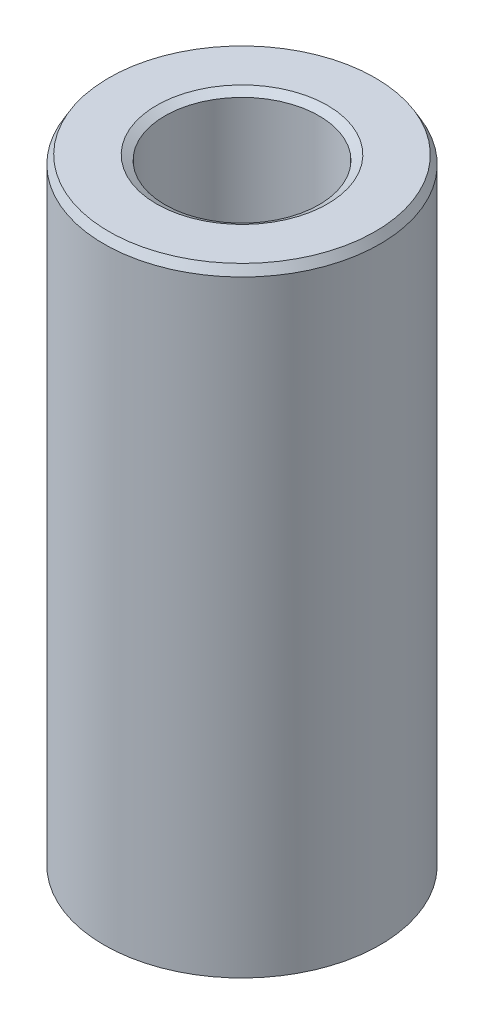
SolidWorks part; units mm, degrees
ref_plane "Front Plane" through (0, 0, 0) normal (0, 0, 1) x (1, 0, 0)
ref_plane "Top Plane" through (0, 0, 0) normal (0, 1, 0) x (1, 0, 0)
ref_plane "Right Plane" through (0, 0, 0) normal (1, 0, 0) x (0, 0, -1)
sketch "Sketch1" plane through (0, 0, 0) normal (0, 1, 0) x (1, 0, 0)
  circle A0 centre (0, 0) radius 52.5
  dimension "SLEEVE_OD" = 105
extrude "Boss-Extrude1" add sketch "Sketch1" along normal blind 235.9374
sketch "Sketch2" plane through (0, 0, 0) normal (0, 1, 0) x (1, 0, 0)
  circle A0 centre (0, 0) radius 29.3129
  dimension "BORE_D" = 58.6259
extrude "Cut-Extrude1" cut sketch "Sketch2" along normal through all
chamfer "Chamfer1" distance 3.1927 angle 30 4 edges at (0, 235.9374, 29.3129) (0, 0, 29.3129) (0, 0, 52.5) (0, 235.9374, 52.5) first distance on face at (0, 235.9374, 29.3129) first distance on face at (0, 0, 29.3129) first distance on face at (0, 235.9374, 52.5)
